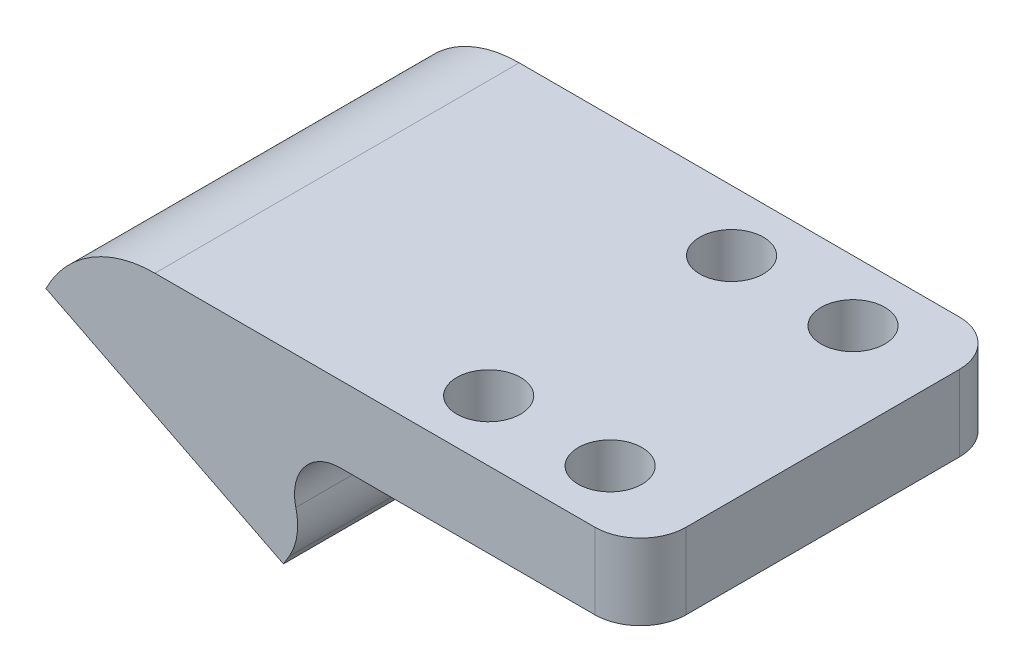
SolidWorks part; units mm, degrees
ref_plane "Plan de face" through (0, 0, 0) normal (0, 0, 1) x (1, 0, 0)
ref_plane "Plan de dessus" through (0, 0, 0) normal (0, 1, 0) x (1, 0, 0)
ref_plane "Plan de droite" through (0, 0, 0) normal (1, 0, 0) x (0, 0, -1)
sketch "Esquisse1" plane through (0, 0, 0) normal (0, 0, 1) x (1, 0, 0)
  line L1 (-6.5596, 0) -> (10.4404, 0)
  line L2 (-6.5596, 0) -> (-6.5596, 5)
  line L3 (-6.5596, 5) -> (10.4404, 5)
  line L4 (10.4404, 0) -> (10.4404, 5)
  dimension "D1" = 5
  dimension "D2" = 17
extrude "Boss.-Extru.1" add sketch "Esquisse1" along normal blind 24
sketch "Esquisse2" plane through (0, 0, 24) normal (0, 0, 1) x (1, 0, 0)
  line L0 (-6.5596, 5) -> (-16.4711, 5)
  line L1 (-16.4711, 5) -> (-0.5016, -3.0561)
  line L2 (-16.4711, 5) -> (-18.7231, 0.5359)
  line L3 (-18.7231, 0.5359) -> (-3.0805, -7.3553)
  line L4 (-3.0805, -7.3553) -> (-0.5016, -3.0561)
  line L5 (-6.5596, 5) -> (-6.5596, 0) construction
  line M4 (-6.5596, 5) -> (-6.5596, 0)
extrude "Boss.-Extru.2" add sketch "Esquisse2" against normal blind 24 contours L3 L4 L1 L2 | L0 L1 M4 region at (-9.8634, 3.3333, 24) region at (-9.6899, -1.2113, 24)
fillet "Congé1" radius 4 1 edges at (-0.5016, -3.0561, 12)
fillet "Congé2" radius 8 1 edges at (-16.4711, 5, 12)
fillet "Congé3" radius 3 1 edges at (-6.5596, 0, 12)
sketch "Esquisse3" plane through (10.4404, 0, 0) normal (1, 0, 0) x (0, 0, -1)
  line L1 (0, 0) -> (-24, 0)
  line L2 (0, 0) -> (0, 5)
  line L3 (0, 5) -> (-24, 5)
  line L4 (-24, 0) -> (-24, 5)
extrude "Boss.-Extru.3" add sketch "Esquisse3" along normal blind 10
sketch "Esquisse4" plane through (0, 5, 0) normal (0, 1, 0) x (1, 0, 0)
  line L0 (14.4404, -4) -> (6.4404, -4) construction
  line L2 (6.4404, -4) -> (6.4404, -20) construction
  line L3 (6.4404, -12) -> (20.4404, -12) construction
  line L4 (20.4404, 0) -> (20.4404, -24) construction
  circle A0 centre (6.4404, -4) radius 2.1
  circle A1 centre (14.4404, -4) radius 2.1
  circle A2 centre (6.4404, -20) radius 2.1
  circle A3 centre (14.4404, -20) radius 2.1
  circle A4 centre (6.4404, -20) radius 2.1
  dimension "D4" = 4.2
  dimension "D1" = 8
  dimension "D2" = 16
  dimension "D3" = 6
extrude "Enlèv. mat.-Extru.1" cut sketch "Esquisse4" against normal blind 10 contours A2 | A3 | A1 | A0 region at (6.4404, 5, 4) region at (14.4404, 5, 4) region at (6.4404, 5, 20) region at (14.4404, 5, 20)
fillet "Congé4" radius 3 2 edges at (20.4404, 2.5, 0) (20.4404, 2.5, 24)
sketch "Esquisse5" plane through (-3.5827, -7.102, 0) normal (-0.4504, -0.8928, 0) x (0.8928, -0.4504, 0)
  line L0 (-16.9578, 12) -> (0.5625, 12) construction
  line L1 (-16.9578, 0) -> (-16.9578, 24) construction
  line L2 (0.5625, 0) -> (0.5625, 24) construction
  line L3 (-12.1477, 8.05) -> (-12.1477, 15.95) construction
  line L4 (-16.9578, 0) -> (0.5625, 0) construction
  line L5 (-8.1977, 0) -> (-8.1977, 24) construction
  line L6 (-16.9578, 24) -> (0.5625, 24) construction
  line L7 (-12.1477, 15.95) -> (-4.2477, 15.95) construction
  line L8 (-4.2477, 15.95) -> (-4.2477, 8.05) construction
  line L9 (-4.2477, 8.05) -> (-12.1477, 8.05) construction
  circle A0 centre (-12.1477, 15.95) radius 1.58 construction
  circle A1 centre (-4.2477, 15.95) radius 1.58 construction
  circle A2 centre (-12.1477, 8.05) radius 1.58 construction
  circle A3 centre (-4.2477, 8.05) radius 1.58 construction
  circle A4 centre (-12.1477, 8.05) radius 2.25
  circle A5 centre (-12.1477, 15.95) radius 2.25
  circle A6 centre (-4.2477, 15.95) radius 2.25
  circle A7 centre (-4.2477, 8.05) radius 2.25
  point P20 (-12.1477, 12)
  point P21 (-8.1977, 8.05)
  dimension "D2" = 3.16
  dimension "D3" = 4.5
  dimension "D1" = 7.9
extrude "Enlèv. mat.-Extru.2" cut sketch "Esquisse5" against normal blind 3
